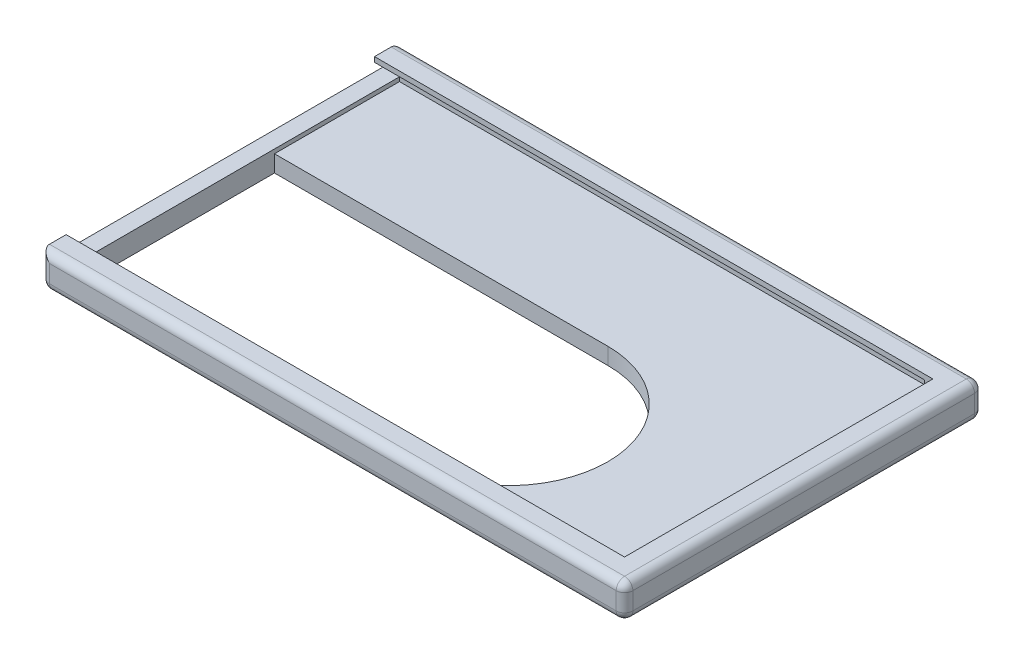
SolidWorks part; units mm, degrees
ref_plane "Front Plane" through (0, 0, 0) normal (0, 0, 1) x (1, 0, 0)
ref_plane "Top Plane" through (0, 0, 0) normal (0, 1, 0) x (1, 0, 0)
ref_plane "Right Plane" through (0, 0, 0) normal (1, 0, 0) x (0, 0, -1)
sketch "Sketch1" plane through (0, 0, 0) normal (0, 1, 0) x (1, 0, 0)
  line L0 (0, -15) -> (40, -15)
  line L1 (0, 0) -> (64, 0)
  line L2 (0, 0) -> (0, -39)
  line L3 (0, -39) -> (64, -39)
  line L4 (66, -1) -> (66, -38)
  line L5 (40, -15) -> (40, -39) construction
  line L6 (-2, 2) -> (68, 2)
  line L7 (68, 2) -> (68, -41)
  line L8 (-2, -41) -> (68, -41)
  line L9 (-2, 2) -> (-2, -41)
  line L10 (52, -27) -> (52, -39) construction
  line L11 (0, 0) -> (66, 0) construction
  line L14 (66, -1) -> (64, -1)
  line L15 (64, 0) -> (64, -1)
  line L18 (66, -38) -> (64, -38)
  line L19 (64, -39) -> (64, -38)
  line L20 (66, 0) -> (66, -39) construction
  line L21 (0, -39) -> (66, -39) construction
  arc A0 (40, -15) -> (40, -39) centre (40, -27) cw
  dimension "D6" = 1
  dimension "D4" = 52
  dimension "D1" = 66
  dimension "D2" = 39
  dimension "D3" = 24
  dimension "D7" = 2
  dimension "D8" = 2
  dimension "D9" = 1
  dimension "D5" = 2
extrude "Boss-Extrude1" add sketch "Sketch1" along normal blind 2 contours L2 L3 L19 L18 L4 L14 L15 L1
extrude "Boss-Extrude2" add sketch "Sketch1<3>" along normal blind 4 contours L6 L9 L8 L7 L1 L4 L3 L2 region at (33, 0, -1.1785)
sketch "Sketch1<3>" plane through (0, 0, 0) normal (0, 1, 0) x (1, 0, 0) same geometry as "Sketch1"
extrude "Cut-Extrude4" cut sketch "Sketch1<5>" along normal up to surface (2 mm away) contours L5 L0 L2 L3 | A0 L5 region at (24.785, 0, 27) up to face at (48.5, 2, 19.5)
sketch "Sketch1<5>" plane through (0, 0, 0) normal (0, 1, 0) x (1, 0, 0) same geometry as "Sketch1"
sketch "Sketch2" plane through (0, 0, 0) normal (1, 0, 0) x (0, 0, -1)
  line L6 (-39, 4) -> (-39, 0) construction
  line L7 (0, 4) -> (-39, 4)
  line L8 (0, 4) -> (0, 2.5)
  line L9 (0, 2.5) -> (-39, 2.5)
  line L10 (-39, 4) -> (-39, 2.5)
  line L11 (0, 2) -> (-15, 2) construction
  dimension "D1" = 0.5
extrude "Cut-Extrude5" cut sketch "Sketch2" against normal up to next
sketch "Sketch3" plane through (0, 4, 0) normal (0, 1, 0) x (1, 0, 0)
  line L0 (-2, -41) -> (68, -41) construction
  line L1 (68, 2) -> (68, -41) construction
  line L2 (-2, 2) -> (68, 2) construction
  line L3 (-2, -41) -> (68, -41)
  line L4 (68, 2) -> (68, -41)
  line L5 (-2, 2) -> (68, 2)
  line L6 (-2, -1) -> (65, -1)
  line L7 (65, -1) -> (65, -38)
  line L8 (-2, -38) -> (65, -38)
  line L9 (-2, -1) -> (-2, 2)
  line L10 (-2, -41) -> (-2, -38)
  dimension "D1" = 3
extrude "Boss-Extrude3" add sketch "Sketch3" along normal blind 0.1 and the other way blind 0.5
fillet "Fillet1" radius 1 11 edges at (-2, 2.05, 41) (33, 4.1, 41) (33, 0, 41) (68, 2.05, 41) (68, 4.1, 19.5) (68, 0, 19.5) (68, 2.05, -2) (33, 4.1, -2) (-2, 2.05, -2) (33, 0, -2) (-2, 0, 19.5)
